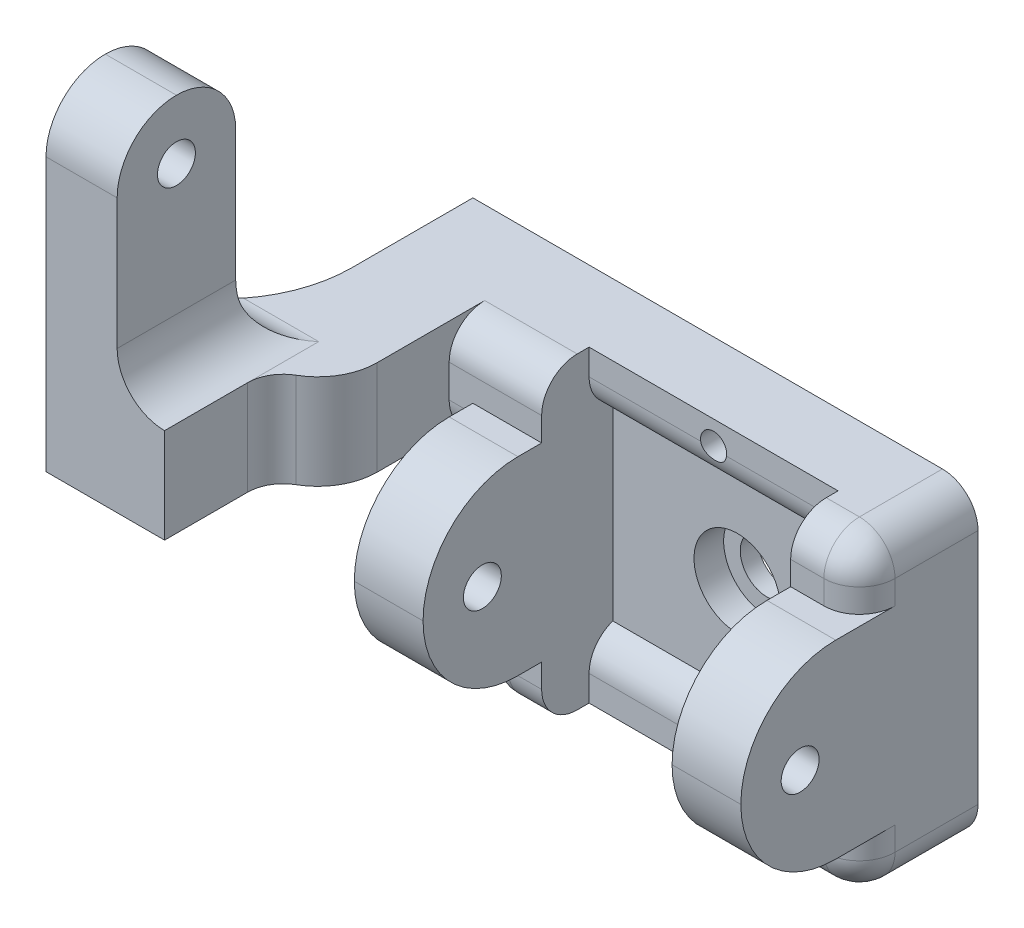
SolidWorks part; units mm, degrees
ref_plane "Front" through (0, 0, 0) normal (0, 0, 1) x (1, 0, 0)
ref_plane "Top" through (0, 0, 0) normal (0, 1, 0) x (1, 0, 0)
ref_plane "Right" through (0, 0, 0) normal (1, 0, 0) x (0, 0, -1)
sketch "Sketch1" plane through (0, 0, 0) normal (0, 0, 1) x (1, 0, 0)
  line L1 (0, 0) -> (-32.6, 0)
  line L2 (0, 0) -> (0, 26)
  line L3 (0, 26) -> (-32.6, 26)
  line L4 (-32.6, 0) -> (-32.6, 26)
  dimension "D1" = 32.6
  dimension "D2" = 26
extrude "Boss-Extrude1" add sketch "Sketch1" along normal blind 4
sketch "Sketch2" plane through (0, 0, 4) normal (0, 0, 1) x (1, 0, 0)
  line L0 (0, 26) -> (-32.6, 26) construction
  line L1 (0, 0) -> (0, 26) construction
  circle A0 centre (-16.3, 13) radius 3.65
  dimension "D1" = 7.3
  dimension "D2" = 13
  dimension "D3" = 16.3
extrude "Cut-Extrude1" cut sketch "Sketch2" against normal blind 2.5
sketch "Sketch3" plane through (0, 0, 1.5) normal (0, 0, 1) x (1, 0, 0)
  circle A0 centre (-16.3, 13) radius 2.25
  dimension "D1" = 4.5
extrude "Cut-Extrude2" cut sketch "Sketch3" against normal through all
sketch "Sketch4" plane through (0, 0, 4) normal (0, 0, 1) x (1, 0, 0)
  line L0 (-32.6, 0) -> (0, 0) construction
  line L1 (0, 26) -> (-5.8, 26)
  line L2 (0, 26) -> (0, 0)
  line L3 (0, 0) -> (-5.8, 0)
  line L4 (-5.8, 26) -> (-5.8, 0)
  line L6 (-32.6, 26) -> (-26.8, 26)
  line L7 (-32.6, 26) -> (-32.6, 0)
  line L8 (-32.6, 0) -> (-26.8, 0)
  line L9 (-26.8, 26) -> (-26.8, 0)
  dimension "D1" = 5.8
  dimension "D2" = 5.8
extrude "Boss-Extrude2" add sketch "Sketch4" along normal blind 16
sketch "Sketch5" plane through (0, 0, 0) normal (1, 0, 0) x (0, 0, -1)
  line L0 (-20, 0) -> (-20, 26) construction
  line L1 (-20, 0) -> (0, 0) construction
  circle A0 centre (-15, 13) radius 1.6
  dimension "D1" = 3.2
  dimension "D2" = 5
  dimension "D3" = 13
extrude "Cut-Extrude3" cut sketch "Sketch5" against normal through all
sketch "Sketch6" plane through (0, 0, 4) normal (0, 0, 1) x (1, 0, 0)
  line L1 (-26.8, 26) -> (-5.8, 26)
  line L2 (-26.8, 26) -> (-26.8, 21)
  line L3 (-26.8, 21) -> (-5.8, 21)
  line L4 (-5.8, 26) -> (-5.8, 21)
  line L5 (-26.8, 0) -> (-5.8, 0)
  line L6 (-26.8, 0) -> (-26.8, 5)
  line L7 (-26.8, 5) -> (-5.8, 5)
  line L8 (-5.8, 0) -> (-5.8, 5)
  dimension "D1" = 5
  dimension "D2" = 5
extrude "Boss-Extrude3" add sketch "Sketch6" along normal blind 2
sketch "Sketch7" plane through (-32.6, 0, 0) normal (-1, 0, 0) x (0, 0, 1)
  line L1 (20, 26) -> (10, 26)
  line L2 (20, 26) -> (20, 21)
  line L3 (20, 21) -> (10, 21)
  line L4 (10, 26) -> (10, 21)
  line L5 (20, 0) -> (10, 0)
  line L6 (20, 0) -> (20, 5)
  line L7 (20, 5) -> (10, 5)
  line L8 (10, 0) -> (10, 5)
  dimension "D1" = 10
  dimension "D2" = 10
  dimension "D3" = 5
  dimension "D4" = 5
extrude "Cut-Extrude4" cut sketch "Sketch7" against normal through all
fillet "Fillet1" radius 8 4 edges at (-2.9, 5, 20) (-2.9, 21, 20) (-29.7, 5, 20) (-29.7, 21, 20)
sketch "Sketch12" plane through (-32.6, 0, 0) normal (-1, 0, 0) x (0, 0, 1)
  line L0 (0, 26) -> (0, 0) construction
  line L1 (10, 26) -> (0, 26)
  line L2 (10, 26) -> (10, 18)
  line L3 (10, 18) -> (0, 18)
  line L4 (0, 26) -> (0, 18)
  dimension "D1" = 8
extrude "Boss-Extrude8" add sketch "Sketch12" along normal blind 10
sketch "Sketch13" plane through (0, 0, 10) normal (0, 0, 1) x (1, 0, 0)
  line L0 (-26.8, 26) -> (-42.6, 26) construction
  line L1 (-42.6, 18) -> (-34.6, 18)
  line L2 (-42.6, 18) -> (-42.6, 26)
  line L3 (-42.6, 26) -> (-34.6, 26)
  line L4 (-34.6, 18) -> (-34.6, 26)
  dimension "D1" = 8
extrude "Boss-Extrude9" add sketch "Sketch13" along normal blind 10
fillet "Fillet2" radius 3 4 edges at (-30.7, 26, 10) (-2.9, 26, 10) (-2.9, 0, 10) (-29.7, 0, 10)
sketch "Sketch14" plane through (0, 0, 20) normal (0, 0, 1) x (1, 0, 0)
  line L0 (-42.6, 18) -> (-34.6, 18) construction
  line L1 (-38.6, 18) -> (-48.6, 18)
  line L2 (-38.6, 18) -> (-38.6, 26)
  line L3 (-38.6, 26) -> (-48.6, 26)
  line L4 (-48.6, 18) -> (-48.6, 26)
  dimension "D1" = 8
  dimension "D2" = 10
extrude "Boss-Extrude10" add sketch "Sketch14" along normal blind 10
sketch "Sketch15" plane through (0, 26, 0) normal (0, 1, 0) x (1, 0, 0)
  line L1 (-48.6, -30) -> (-42.6, -30)
  line L2 (-48.6, -30) -> (-48.6, -20)
  line L3 (-48.6, -20) -> (-42.6, -20)
  line L4 (-42.6, -30) -> (-42.6, -20)
  dimension "D1" = 10
  dimension "D2" = 6
extrude "Boss-Extrude11" add sketch "Sketch15" along normal blind 20
fillet "Fillet10" radius 11 1 edges at (-42.6, 22, 20)
fillet "Fillet11" radius 3 1 edges at (-38.6, 22, 20)
fillet "Fillet12" radius 5 1 edges at (-34.6, 22, 20)
fillet "Fillet14" radius 4 1 edges at (-42.6, 26, 25)
fillet "Fillet15" radius 3 1 edges at (-43.6, 26, 20)
sketch "Sketch16" plane through (0, 0, 0) normal (0, 0, -1) x (-1, 0, 0)
  line L0 (42.6, 18) -> (32.6, 18)
  line L1 (32.6, 18) -> (32.6, 9)
  line L2 (32.6, 18) -> (32.6, 0) construction
  line L3 (32.6, 9) -> (42.6, 18)
  dimension "D1" = 9
extrude "Boss-Extrude12" add sketch "Sketch16" against normal blind 9
fillet "Fillet17" radius 3 1 edges at (-32.6, 9, 4.5)
fillet "Fillet18" radius 3 1 edges at (-33.6, 18, 10)
sketch "Sketch17" plane through (-48.6, 0, 0) normal (-1, 0, 0) x (0, 0, 1)
  line L0 (30, 46) -> (30, 18) construction
  line L1 (20, 46) -> (30, 46) construction
  circle A0 centre (25, 41) radius 1.6
  dimension "D1" = 3.2
  dimension "D2" = 5
  dimension "D3" = 5
extrude "Cut-Extrude5" cut sketch "Sketch17" against normal through all
fillet "Fillet19" radius 5 2 edges at (-45.6, 46, 20) (-45.6, 46, 30)
fillet "Fillet21" radius 3 2 edges at (-16.3, 21, 6) (-16.3, 5, 6)
fillet "Fillet22" radius 3 9 edges at (0, 22, 10) (0, 25.1213, 9.1213) (0, 4, 10) (0, 0.8787, 9.1213) (-32.6, 4, 10) (-32.6, 0.8787, 9.1213) (0, 26, 3.5) (0, 0, 3.5) (-32.6, 0, 3.5)
sketch "Sketch18" plane through (0, 0, 0) normal (0, 0, -1) x (-1, 0, 0)
  line L0 (29.6, 0) -> (3, 0) construction
  line L1 (3, 26) -> (42.6, 26) construction
  line L2 (0, 3) -> (0, 23) construction
  line L3 (32.6, 7.6639) -> (32.6, 3) construction
  circle A0 centre (16.3, 2) radius 1.1
  circle A1 centre (3.5, 13) radius 1.25
  circle A2 centre (29.1, 13) radius 1.25
  circle A3 centre (16.3, 24) radius 1.1
  dimension "D1" = 2.2
  dimension "D2" = 2.2
  dimension "D3" = 2.5
  dimension "D4" = 2.5
  dimension "D5" = 2
  dimension "D6" = 2
  dimension "D7" = 3.5
  dimension "D8" = 3.5
  dimension "D9" = 13
extrude "Cut-Extrude6" cut sketch "Sketch18" against normal blind 8
